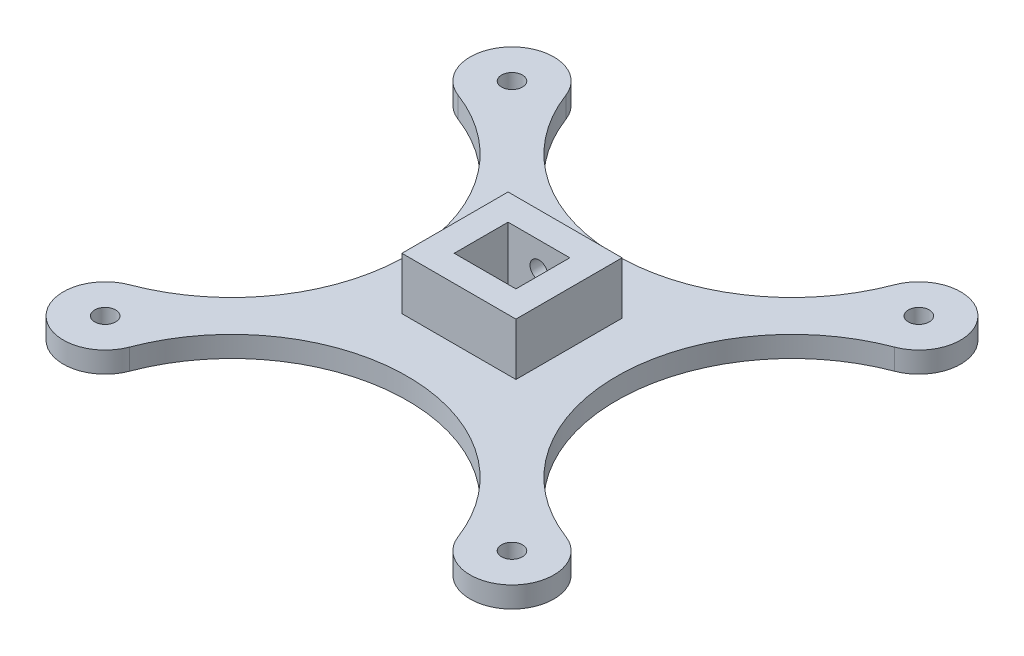
SolidWorks part; units mm, degrees
material "PET"
ref_plane "Front Plane" through (0, 0, 0) normal (0, 0, 1) x (1, 0, 0)
ref_plane "Top Plane" through (0, 0, 0) normal (0, 1, 0) x (1, 0, 0)
ref_plane "Right Plane" through (0, 0, 0) normal (1, 0, 0) x (0, 0, -1)
sketch "Sketch1" plane through (0, 0, 0) normal (0, 1, 0) x (1, 0, 0)
  line L22 (0, -7.7) -> (0, 7.7) construction
  line L23 (-38.8909, 38.8909) -> (38.8909, -38.8909) construction
  line L24 (38.8909, 38.8909) -> (-38.8909, -38.8909) construction
  line L29 (0, 20) -> (0, -20) construction
  line L31 (-20, 0) -> (20, 0) construction
  circle A8 centre (0, 0) radius 55 construction
  circle A9 centre (-38.8909, 38.8909) radius 2
  circle A10 centre (38.8909, 38.8909) radius 2
  circle A11 centre (38.8909, -38.8909) radius 2
  circle A12 centre (-38.8909, -38.8909) radius 2
  arc A13 (-31.4062, 41.7156) -> (-41.7156, 31.4062) centre (-38.8909, 38.8909) ccw
  arc A14 (41.7156, 31.4062) -> (31.4062, 41.7156) centre (38.8909, 38.8909) ccw
  arc A15 (31.4062, -41.7156) -> (41.7156, -31.4062) centre (38.8909, -38.8909) ccw
  arc A16 (-41.7156, -31.4062) -> (-31.4062, -41.7156) centre (-38.8909, -38.8909) ccw
  arc A17 (-41.7156, 31.4062) -> (-41.7156, -31.4062) centre (-53.5684, 0) cw
  arc A18 (41.7156, 31.4062) -> (41.7156, -31.4062) centre (53.5684, 0) ccw
  arc A19 (-31.4062, 41.7156) -> (31.4062, 41.7156) centre (0, 53.5684) ccw
  arc A20 (-31.4062, -41.7156) -> (31.4062, -41.7156) centre (0, -53.5684) cw
  point P14 (0, 0)
  point P34 (0, 0)
  dimension "D1" = 40
  dimension "D6" = 4
  dimension "D7" = 110
  dimension "D8" = 8
extrude "Boss-Extrude1" add sketch "Sketch1" along normal blind 4
sketch "Sketch7" plane through (0, 4, 0) normal (0, -1, 0) x (1, 0, 0)
  line L0 (-10.9, 10.15) -> (10.9, 10.15)
  line L1 (-5.9, -5.15) -> (5.9, -5.15)
  line L2 (-5.9, -5.15) -> (-5.9, 5.15)
  line L3 (-5.9, 5.15) -> (5.9, 5.15)
  line L4 (5.9, -5.15) -> (5.9, 5.15)
  line L5 (-5.9, -5.15) -> (5.9, 5.15) construction
  line L6 (-5.9, 5.15) -> (5.9, -5.15) construction
  line L7 (10.9, -10.15) -> (10.9, 10.15)
  line L8 (-10.9, -10.15) -> (10.9, -10.15)
  line L9 (-10.9, -10.15) -> (-10.9, 10.15)
  point P0 (0, 0)
  dimension "D1" = 11.8
  dimension "D2" = 10.3
  dimension "D3" = 5
extrude "Boss-Extrude2" add sketch "Sketch7" against normal blind 10
hole_wizard "M3 Clearance Hole1" positions "3DSketch1" profile "Sketch8" hole size "M3" standard "ISO" end condition up to next
sketch3d "3DSketch1"
  line L0 (10.9, 14, -10.15) -> (10.9, 4, -10.15) construction
  line L2 (-10.9, 14, -10.15) -> (10.9, 14, -10.15) construction
  point P0 (0, 9, -10.15)
  dimension "D1" = 10.9
  dimension "D2" = 5
sketch "Sketch8" plane through (0, 9, -10.15) normal (1, 0, 0) x (0, 1, 0)
  line L0 (0, 0) -> (0, 5)
  line L1 (0, 5) -> (1.7, 5)
  line L2 (1.7, 5) -> (1.7, 0)
  line L5 (1.7, 0) -> (0, 0)
  line L11 (0, -6.35) -> (0, 107.95) construction
  dimension "Thru Hole Dia." = 3.4
  dimension "Thru Hole Depth" = 5
extrude "Cut-Extrude1" cut sketch "Sketch7<2>" along normal blind 10 contours L3 L4 L1 L2
sketch "Sketch7<2>" plane through (0, 4, 0) normal (0, -1, 0) x (1, 0, 0) same geometry as "Sketch7"
